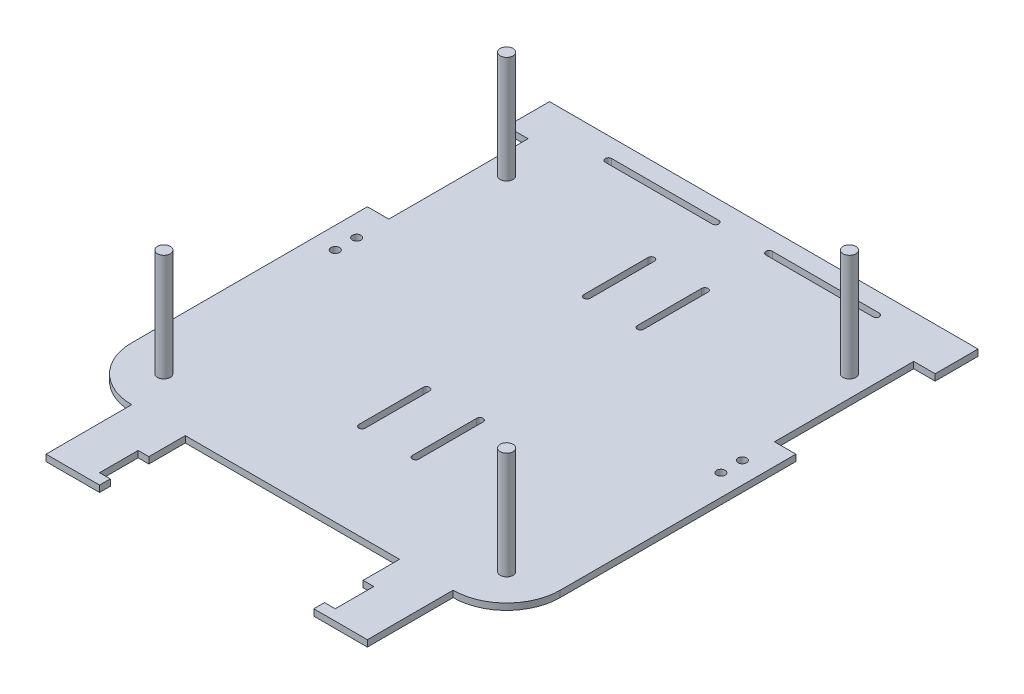
SolidWorks part; units mm, degrees
ref_plane "Front Plane" through (0, 0, 0) normal (0, 0, 1) x (1, 0, 0)
ref_plane "Top Plane" through (0, 0, 0) normal (0, 1, 0) x (1, 0, 0)
ref_plane "Right Plane" through (0, 0, 0) normal (1, 0, 0) x (0, 0, -1)
sketch "Sketch1" plane through (0, 0, 0) normal (0, 1, 0) x (1, 0, 0)
  line L0 (12.5, 210) -> (62.5, 210) construction
  line L1 (-75, 0) -> (75, 0)
  line L2 (0, 0) -> (0, 220) construction
  line L3 (-100, 220) -> (100, 220)
  line L4 (100, 25) -> (100, 220)
  line L5 (100, 200) -> (90, 200)
  line L6 (100, 200) -> (100, 135)
  line L7 (100, 135) -> (90, 135)
  line L8 (90, 200) -> (90, 135)
  line L9 (12.5, 211.5) -> (62.5, 211.5)
  line L10 (12.5, 208.5) -> (62.5, 208.5)
  line L11 (12.5, 180) -> (12.5, 150) construction
  line L12 (14, 180) -> (14, 150)
  line L13 (11, 180) -> (11, 150)
  line L14 (12.5, 75) -> (12.5, 45) construction
  line L15 (14, 75) -> (14, 45)
  line L16 (11, 75) -> (11, 45)
  line L17 (-90, 200) -> (-90, 135)
  line L18 (-100, 135) -> (-90, 135)
  line L19 (-100, 200) -> (-100, 135)
  line L20 (-100, 200) -> (-90, 200)
  line L21 (-100, 25) -> (-100, 220)
  line L22 (-12.5, 75) -> (-12.5, 45) construction
  line L23 (-14, 75) -> (-14, 45)
  line L24 (-11, 75) -> (-11, 45)
  line L25 (-12.5, 180) -> (-12.5, 150) construction
  line L26 (-14, 180) -> (-14, 150)
  line L27 (-11, 180) -> (-11, 150)
  line L28 (-12.5, 210) -> (-62.5, 210) construction
  line L29 (-12.5, 211.5) -> (-62.5, 211.5)
  line L30 (-12.5, 208.5) -> (-62.5, 208.5)
  line L31 (-50, -40) -> (-50, -35)
  line L32 (-75, 0) -> (-50, 0)
  line L33 (-75, 0) -> (-75, -40)
  line L34 (-75, -40) -> (-50, -40)
  line L35 (-50, 0) -> (-50, -40)
  line L36 (75, 0) -> (50, 0)
  line L37 (75, 0) -> (75, -40)
  line L38 (75, -40) -> (50, -40)
  line L39 (50, 0) -> (50, -40)
  line L40 (50, -40) -> (49.9323, -39.7896)
  line L41 (50, -40) -> (50, -35)
  line L43 (-50, -35) -> (-55, -35)
  line L44 (-50, -35) -> (-50, -17)
  line L45 (-50, -17) -> (-55, -17)
  line L46 (-55, -35) -> (-55, -17)
  line L47 (50, -35) -> (55, -35)
  line L48 (50, -35) -> (50, -17)
  line L49 (50, -17) -> (55, -17)
  line L50 (55, -35) -> (55, -17)
  arc A0 (12.5, 211.5) -> (12.5, 208.5) centre (12.5, 210) ccw
  arc A1 (62.5, 208.5) -> (62.5, 211.5) centre (62.5, 210) ccw
  circle A2 centre (90, 120) radius 2
  circle A3 centre (90, 110) radius 2
  arc A4 (14, 180) -> (11, 180) centre (12.5, 180) ccw
  arc A5 (11, 150) -> (14, 150) centre (12.5, 150) ccw
  arc A6 (75, 0) -> (100, 25) centre (75, 25) ccw
  arc A7 (14, 75) -> (11, 75) centre (12.5, 75) ccw
  arc A8 (11, 45) -> (14, 45) centre (12.5, 45) ccw
  arc A9 (-75, 0) -> (-100, 25) centre (-75, 25) cw
  circle A10 centre (-90, 110) radius 2
  circle A11 centre (-90, 120) radius 2
  arc A12 (-14, 75) -> (-11, 75) centre (-12.5, 75) cw
  arc A13 (-11, 45) -> (-14, 45) centre (-12.5, 45) cw
  arc A14 (-14, 180) -> (-11, 180) centre (-12.5, 180) cw
  arc A15 (-11, 150) -> (-14, 150) centre (-12.5, 150) cw
  arc A16 (-12.5, 211.5) -> (-12.5, 208.5) centre (-12.5, 210) cw
  arc A17 (-62.5, 208.5) -> (-62.5, 211.5) centre (-62.5, 210) cw
  point P11 (37.5, 210)
  point P22 (12.5, 165)
  point P29 (100, 0)
  point P32 (12.5, 60)
  point P51 (-12.5, 60)
  point P56 (-100, 0)
  point P59 (-12.5, 165)
  point P66 (-37.5, 210)
  dimension "D9" = 10
  dimension "D11" = 4
  dimension "D14" = 4
  dimension "D19" = 25
  dimension "D23" = 1.5
  dimension "D1" = 100
  dimension "D2" = 220
  dimension "D3" = 65
  dimension "D4" = 10
  dimension "D5" = 50
  dimension "D6" = 37.5
  dimension "D7" = 3
  dimension "D8" = 10
  dimension "D10" = 100
  dimension "D12" = 10
  dimension "D13" = 10
  dimension "D15" = 3
  dimension "D16" = 30
  dimension "D17" = 20
  dimension "D18" = 55
  dimension "D20" = 3
  dimension "D21" = 30
  dimension "D22" = 12.5
  dimension "D24" = 60
  dimension "D25" = 25
  dimension "D26" = 25
  dimension "D27" = 40
  dimension "D28" = 40
  dimension "D29" = 5
  dimension "D30" = 18
  dimension "D31" = 18
  dimension "D32" = 5
  dimension "D33" = 5
extrude "Boss-Extrude1" add sketch "Sketch1" along normal blind 3 contours A9 L1 A6 L4 L7 L8 L5 L3 L21 L20 L17 L18 L27 A15 L26 A14 A11 A1 L10 A0 L9 A2 A3 A5 L13 A4 L12 A8 L16 A7 L15 A10 L24 A13 L23 A12 L30 A17 L29 region at (0, 0, -108.0955)
sketch "Sketch2" plane through (0, 3, 0) normal (0, 1, 0) x (1, 0, 0)
  line L0 (-100, 25) -> (-100, 135) construction
  line L1 (90, 200) -> (90, 135) construction
  line L2 (-75, 0) -> (75, 0) construction
  line L3 (-90, 200) -> (-90, 135) construction
  line L4 (-100, 220) -> (100, 220) construction
  circle A0 centre (-80, 20) radius 3
  circle A1 centre (80, 20) radius 3
  circle A2 centre (-80, 180) radius 3
  circle A3 centre (80, 180) radius 3
  dimension "D5" = 6
  dimension "D6" = 6
  dimension "D7" = 6
  dimension "D10" = 6
  dimension "D1" = 20
  dimension "D2" = 20
  dimension "D3" = 160
  dimension "D4" = 20
  dimension "D8" = 10
  dimension "D9" = 40
  dimension "D11" = 10
  dimension "D12" = 40
extrude "Boss-Extrude2" add sketch "Sketch2" along normal blind 50
sketch "Sketch3" plane through (0, 0, 0) normal (0, 1, 0) x (1, 0, 0)
  line L0 (100, 25) -> (100, 135) construction
  line L1 (-75, 0) -> (75, 0) construction
  line L2 (100, 25) -> (-100, 25)
  line L3 (-43.4, 50) -> (-100, 50)
  line L4 (-100, 25) -> (-100, 135) construction
  circle A0 centre (-43.4, 50) radius 3.8
  circle A1 centre (43.4, 50) radius 3.8
  dimension "D1" = 86.8
  dimension "D4" = 7.6
  dimension "D5" = 7.6
  dimension "D2" = 56.6
  dimension "D3" = 50
  dimension "D6" = 50
extrude "Boss-Extrude3" add sketch "Sketch3" against normal blind 30 contours A1 | A0
extrude "Boss-Extrude4" add sketch "Sketch1<3>" along normal blind 3 contours L33 L34 L35 L32 | L36 L39 L38 L37
sketch "Sketch1<3>" plane through (0, 0, 0) normal (0, 1, 0) x (1, 0, 0) same geometry as "Sketch1"
sketch "Sketch4" plane through (0, 3, 0) normal (0, 1, 0) x (1, 0, 0)
  line L0 (-50, -40) -> (-50, -35)
  line L1 (-50, 0) -> (-50, -40) construction
  line L2 (50, -40) -> (50, -35)
  line L3 (50, 0) -> (50, -40) construction
  line L5 (-50, -35) -> (-55, -35)
  line L6 (-50, -35) -> (-50, -17)
  line L7 (-50, -17) -> (-55, -17)
  line L8 (-55, -35) -> (-55, -17)
  line L9 (50, -35) -> (55, -35)
  line L10 (50, -35) -> (50, -17)
  line L11 (50, -17) -> (55, -17)
  line L12 (55, -35) -> (55, -17)
  dimension "D1" = 5
  dimension "D2" = 5
  dimension "D3" = 18
  dimension "D4" = 5
  dimension "D5" = 5
  dimension "D6" = 18
extrude "Cut-Extrude1" cut sketch "Sketch4" against normal blind 10 contours L8 L5 L6 L7 | L9 L12 L11 L10 region at (-52.5, 3, 26) region at (52.5, 3, 26)
